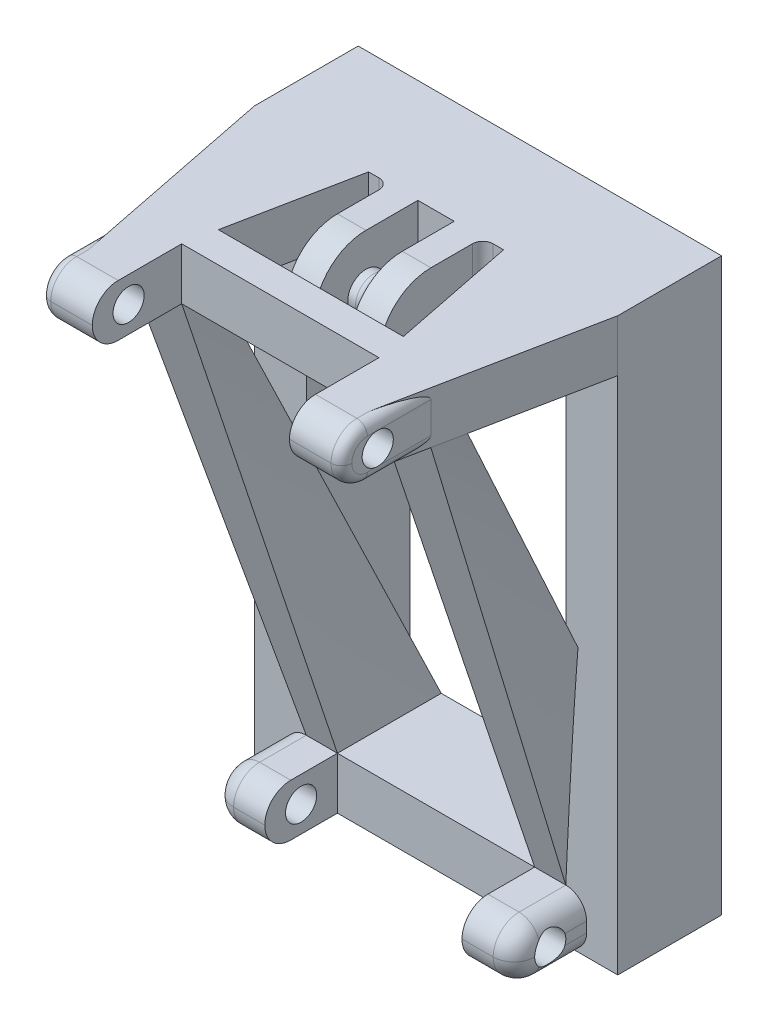
SolidWorks part; units mm, degrees
ref_plane "Front Plane" through (0, 0, 0) normal (0, 0, 1) x (1, 0, 0)
ref_plane "Top Plane" through (0, 0, 0) normal (0, 1, 0) x (1, 0, 0)
ref_plane "Right Plane" through (0, 0, 0) normal (1, 0, 0) x (0, 0, -1)
sketch "Sketch1" plane through (0, 0, 0) normal (0, 0, 1) x (1, 0, 0)
  line L1 (-17.5, -27.5) -> (17.5, -27.5)
  line L2 (-17.5, -27.5) -> (-17.5, 27.5)
  line L3 (-17.5, 27.5) -> (17.5, 27.5)
  line L4 (17.5, -27.5) -> (17.5, 27.5)
  line L5 (-17.5, -27.5) -> (17.5, 27.5) construction
  line L6 (-17.5, 27.5) -> (17.5, -27.5) construction
  point P0 (0, 0)
  dimension "D1" = 35
  dimension "D2" = 55
extrude "Boss-Extrude1" add sketch "Sketch1" along normal blind 3
sketch "Sketch2" plane through (0, 0, 3) normal (0, 0, 1) x (1, 0, 0)
  line L18 (-14.5, 27.5) -> (-9.5, 27.5)
  line L19 (-14.5, 27.5) -> (-14.5, 22.5)
  line L20 (-9.5, 27.5) -> (-9.5, 22.5)
  line L21 (-14.5, 22.5) -> (-9.5, 22.5)
  line L22 (17.5, 27.5) -> (-17.5, 27.5) construction
  line L23 (9.5, 27.5) -> (14.5, 27.5)
  line L24 (9.5, 27.5) -> (9.5, 22.5)
  line L25 (14.5, 27.5) -> (14.5, 22.5)
  line L26 (9.5, 22.5) -> (14.5, 22.5)
  line L27 (-9.5, -27.5) -> (-14.5, -27.5)
  line L28 (-9.5, -27.5) -> (-9.5, -22.5)
  line L29 (-14.5, -27.5) -> (-14.5, -22.5)
  line L30 (-9.5, -22.5) -> (-14.5, -22.5)
  line L31 (-17.5, -27.5) -> (17.5, -27.5) construction
  line L32 (9.5, -27.5) -> (14.5, -27.5)
  line L33 (9.5, -27.5) -> (9.5, -22.5)
  line L34 (14.5, -27.5) -> (14.5, -22.5)
  line L35 (9.5, -22.5) -> (14.5, -22.5)
  line L36 (-17.5, 27.5) -> (-17.5, -27.5) construction
  line L37 (17.5, -27.5) -> (17.5, 27.5) construction
  dimension "D1" = 5
  dimension "D2" = 3
  dimension "D3" = 3
  dimension "D4" = 3
  dimension "D5" = 3
  dimension "D6" = 5
extrude "Boss-Extrude2" add sketch "Sketch2" along normal blind 7
sketch "Sketch3" plane through (-14.5, 0, 0) normal (-1, 0, 0) x (0, 0, 1)
  line L0 (3, 27.5) -> (10, 22.5)
  line L1 (3, -22.5) -> (10, -27.5)
  circle A0 centre (6.5, 25) radius 1.5
  circle A1 centre (6.5, -25) radius 1.5
  dimension "D1" = 3
  dimension "D2" = 3
extrude "Cut-Extrude1" cut sketch "Sketch3" against normal up to surface (29 mm away) contours L1 A1 | L1 A1 region at (-14.5, -24.482, 6.87) region at (-14.5, -25.518, 6.13) up to face at (14.5, 25, 6.5)
fillet "Fillet1" radius 2.5 4 edges at (12, -27.5, 10) (12, -22.5, 10) (-12, -27.5, 10) (-12, -22.5, 10)
sketch "Sketch4" plane through (0, 0, 10) normal (0, 0, 1) x (1, 0, 0)
  line L1 (-9.5, 27.5) -> (-14.5, 27.5)
  line L2 (-9.5, 27.5) -> (-9.5, 22.5)
  line L3 (-9.5, 22.5) -> (-14.5, 22.5)
  line L4 (-14.5, 27.5) -> (-14.5, 22.5)
  line L5 (14.5, 27.5) -> (9.5, 27.5)
  line L6 (14.5, 27.5) -> (14.5, 22.5)
  line L7 (14.5, 22.5) -> (9.5, 22.5)
  line L8 (9.5, 27.5) -> (9.5, 22.5)
extrude "Boss-Extrude3" add sketch "Sketch4" along normal blind 16.6176
sketch "Sketch5" plane through (-14.5, 0, 0) normal (-1, 0, 0) x (0, 0, 1)
  line L0 (26.6176, 22.5) -> (3, 22.5) construction
  line L1 (26.6176, 27.5) -> (19.6176, 27.5)
  line L2 (26.6176, 27.5) -> (26.6176, 22.5)
  line L3 (26.6176, 22.5) -> (19.6176, 22.5)
  line L4 (19.6176, 27.5) -> (19.6176, 22.5)
  line L5 (19.6176, 27.5) -> (26.6176, 22.5)
  circle A0 centre (23.1176, 25) radius 1.5
  dimension "D2" = 3
  dimension "D1" = 7
extrude "Cut-Extrude2" cut sketch "Sketch5" against normal up to surface (29 mm away) contours L5 A0 | L5 A0 region at (-14.5, 25.518, 23.4877) region at (-14.5, 24.482, 22.7476) up to face at (14.5, 25, 14.8088)
fillet "Fillet2" radius 2.5 4 edges at (12, 22.5, 26.6176) (12, 27.5, 26.6176) (-12, 22.5, 26.6176) (-12, 27.5, 26.6176)
fillet "Fillet3" radius 2 8 edges at (-14.5, -27.5, 5.25) (-14.5, -26.7678, 9.2678) (-14.5, -22.5, 5.25) (14.5, -22.5, 5.25) (14.5, -27.5, 5.25) (14.5, -26.7678, 9.2678) (-14.5, -23.2322, 9.2678) (14.5, -23.2322, 9.2678)
chamfer "Chamfer1" distance 3 distance2 15 2 edges at (-14.5, 25, 3) (14.5, 25, 3) first distance on face at (0, -4.1667, 3)
fillet "Fillet5" radius 1 8 edges at (-14.5, 22.5, 21.0588) (-14.5, 23.2322, 25.8854) (-14.5, 27.5, 21.0588) (14.5, 27.5, 21.0588) (14.5, 22.5, 21.0588) (14.5, 23.2322, 25.8854) (-14.5, 26.7678, 25.8854) (14.5, 26.7678, 25.8854)
sketch "Sketch6" plane through (0, 0, 3) normal (0, 0, 1) x (1, 0, 0)
  line L0 (-4.5, 27.5) -> (4.5, 27.5)
  line L1 (9.5, 27.5) -> (-9.5, 27.5) construction
  line L3 (-4.5, 27.5) -> (-1.75, 27.5)
  line L4 (-4.5, 27.5) -> (-4.5, 17.5)
  line L5 (-4.5, 17.5) -> (-1.75, 17.5)
  line L6 (-1.75, 27.5) -> (-1.75, 17.5)
  line L7 (4.5, 27.5) -> (1.75, 27.5)
  line L8 (4.5, 27.5) -> (4.5, 17.5)
  line L9 (4.5, 17.5) -> (1.75, 17.5)
  line L10 (1.75, 27.5) -> (1.75, 17.5)
  point P5 (0, 27.5)
  line M28 (9.5, 27.5) -> (-9.5, 27.5)
  dimension "D1" = 9
  dimension "D2" = 2.75
  dimension "D3" = 10
extrude "Boss-Extrude4" add sketch "Sketch6" along normal blind 10 contours L6 L0 L4 L5 | L10 L9 L8 M28 region at (3.125, 22.5, 3) region at (-3.125, 22.5, 3)
sketch "Sketch7" plane through (-4.5, 0, 0) normal (-1, 0, 0) x (0, 0, 1)
  line L0 (3, 27.5) -> (13, 17.5)
  circle A0 centre (8, 22.5) radius 1.75
  dimension "D1" = 3.5
fillet "Fillet6" radius 5 4 edges at (-3.125, 17.5, 13) (3.125, 17.5, 13) (3.125, 27.5, 13) (-3.125, 27.5, 13)
fillet "Fillet7" radius 1 2 edges at (-4.5, 22.5, 3) (4.5, 22.5, 3)
extrude "Boss-Extrude5" add sketch "Sketch7" against normal blind 1.25 from surface contours L0 A0 | L0 A0 region at (-4.5, 23.0252, 8.5252) region at (-4.5, 21.9748, 7.4748) starting at face at (-1.75, 22.5, 7.4142)
sketch "Sketch9" plane through (4.5, 0, 0) normal (1, 0, 0) x (0, 0, -1)
  line L0 (-8, 17.5) -> (-8, 27.5)
  circle A0 centre (-8, 22.5) radius 1.75
  dimension "D1" = 3.5
extrude "Boss-Extrude6" add sketch "Sketch9" against normal blind 1.25 from surface contours L0 A0 | L0 A0 region at (4.5, 22.5, 8.7427) region at (4.5, 22.5, 7.2573) starting at face at (1.75, 22.5, 7.4142)
chamfer "Chamfer2" distance 3 distance2 15 2 edges at (9.5, 25, 3) (-9.5, 25, 3) first distance on face at (0, -1.0714, 3)
sketch "Sketch10" plane through (5.6731, 0, -1.1346) normal (-0.9806, 0, 0.1961) x (0.1961, 0, 0.9806)
  line L0 (19.5136, 22.5) -> (4.2165, 22.5) construction
  line L1 (19.5136, 27.5) -> (16.5136, 27.5)
  line L2 (19.5136, 27.5) -> (19.5136, 22.5)
  line L3 (19.5136, 22.5) -> (16.5136, 22.5)
  line L4 (16.5136, 27.5) -> (16.5136, 22.5)
  dimension "D1" = 3
extrude "Boss-Extrude7" add sketch "Sketch10" along direction (-1, 0, 0) on the side of the normal up to surface (19 mm away) up to face at (-8, 25, 10.5)
fillet "Fillet8" radius 0.5 2 edges at (0.5, 24.25, 8) (-0.5, 24.25, 8)
sketch "Sketch12" plane through (0, 22.5, 0) normal (0, -1, 0) x (1, 0, 0)
  line L0 (-9.5, 18) -> (-8.9117, 15.0583)
  line L1 (-8.9117, 15.0583) -> (-15.0883, 15.0583)
  line L2 (-13.5, 23) -> (-17.5, 3) construction
  line L3 (-15.0883, 15.0583) -> (-14.5, 18)
  line L4 (-14.5, 18) -> (-9.5, 18)
sketch "Sketch13" plane through (0, 22.5, 0) normal (0, -1, 0) x (1, 0, 0)
  line L0 (9.5, 18) -> (8.9117, 15.0583)
  line L1 (8.9117, 15.0583) -> (15.0883, 15.0583)
  line L2 (17.5, 3) -> (13.5, 23) construction
  line L3 (15.0883, 15.0583) -> (14.5, 18)
  line L4 (14.5, 18) -> (9.5, 18)
sketch "Sketch15" plane through (0, 0, 0) normal (0, 0, -1) x (-1, 0, 0)
  line L1 (-17.5, 27.5) -> (17.5, 27.5)
  line L2 (-17.5, 27.5) -> (-17.5, -27.5)
  line L3 (-17.5, -27.5) -> (17.5, -27.5)
  line L4 (17.5, 27.5) -> (17.5, -27.5)
extrude "Boss-Extrude8" add sketch "Sketch15" along normal blind 7
sketch "Sketch16" plane through (0, 0, 3) normal (0, 0, 1) x (1, 0, 0)
  line L0 (-17.5, 22.5) -> (-17.5, -27.5) construction
  line L1 (-17.5, -22.5) -> (17.5, -22.5)
  line L2 (-17.5, -22.5) -> (-17.5, 17.5)
  line L3 (-17.5, 17.5) -> (17.5, 17.5)
  line L4 (17.5, -22.5) -> (17.5, 17.5)
  line L5 (17.5, -27.5) -> (17.5, 22.5) construction
  line L6 (5.5, 17.5) -> (1.75, 17.5) construction
  line L7 (-9.5, -22.5) -> (-12.5, -22.5) construction
  line L8 (5.5, 17.5) -> (17.5, 22.5)
  line L9 (17.5, 22.5) -> (17.5, 17.5)
  line L10 (-5.5, 17.5) -> (-17.5, 22.5)
  line L11 (-17.5, 22.5) -> (-17.5, 17.5)
  line M9 (5.5, 17.5) -> (1.75, 17.5)
  line M13 (-1.75, 17.5) -> (-5.5, 17.5)
  line M18 (-17.5, 22.5) -> (-17.5, -27.5)
  line M23 (-12.5, -22.5) -> (-9.5, -22.5)
  line M27 (9.5, -22.5) -> (12.5, -22.5)
  line M32 (17.5, -27.5) -> (17.5, 22.5)
extrude "Cut-Extrude5" cut sketch "Sketch16" against normal up to surface (10 mm away) contours L3 L10 M18 | L8 L3 M32 | L3 L1 M18 M23 M27 M32 M9 M13 region at (0, -2.5, 3) region at (-13.5, 19.1667, 3) region at (13.5, 19.1667, 3) up to face at (0, 0, -7)
sketch "Sketch17" plane through (0, -22.5, 0) normal (0, 1, 0) x (1, 0, 0)
  line L0 (-17.5, 7) -> (17.5, 7) construction
  line L1 (12.5, -3) -> (9.5, -3)
  line L2 (12.5, -3) -> (12.5, 7)
  line L3 (12.5, 7) -> (9.5, 7)
  line L4 (9.5, -3) -> (9.5, 7)
  point P7 (0, 0)
sketch "Sketch18" plane through (0, -22.5, 0) normal (0, 1, 0) x (1, 0, 0)
  line L0 (-17.5, 7) -> (17.5, 7) construction
  line L1 (-12.5, -3) -> (-9.5, -3)
  line L2 (-12.5, -3) -> (-12.5, 7)
  line L3 (-12.5, 7) -> (-9.5, 7)
  line L4 (-9.5, -3) -> (-9.5, 7)
  point P7 (0, 0)
loft "Loft3" add profiles "Sketch13", "Sketch17" connector at (15.0883, 22.5, 15.0583) connector at (12.5, -22.5, -7)
loft "Loft4" add profiles "Sketch12", "Sketch18" connector at (-8.9117, 22.5, 15.0583) connector at (-9.5, -22.5, -7)
sketch "Sketch19" plane through (0, -22.5, 0) normal (0, 1, 0) x (1, 0, 0)
  line L1 (17.5, -3) -> (12.5, -3)
  line L2 (17.5, -3) -> (17.5, 7)
  line L3 (17.5, 7) -> (12.5, 7)
  line L4 (12.5, -3) -> (12.5, 7)
  line L5 (-17.5, -3) -> (-12.5, -3)
  line L6 (-17.5, -3) -> (-17.5, 7)
  line L7 (-17.5, 7) -> (-12.5, 7)
  line L8 (-12.5, -3) -> (-12.5, 7)
extrude "Boss-Extrude9" add sketch "Sketch19" along normal up to surface (50 mm away) up to face at (0, 27.5, 6.2645)
